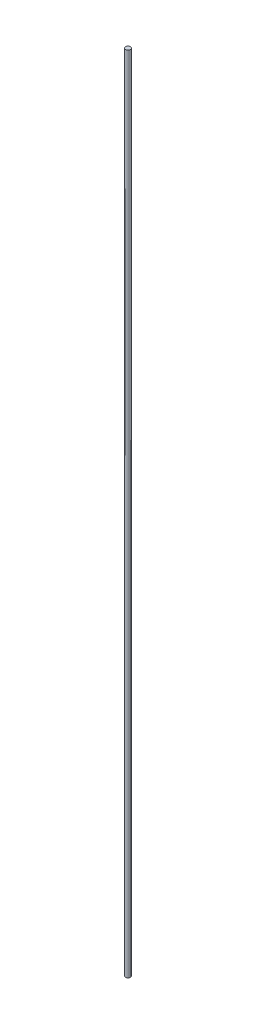
SolidWorks part; units mm, degrees
ref_plane "Спереди" through (0, 0, 0) normal (0, 0, 1) x (1, 0, 0)
ref_plane "Сверху" through (0, 0, 0) normal (0, 1, 0) x (1, 0, 0)
ref_plane "Справа" through (0, 0, 0) normal (1, 0, 0) x (0, 0, -1)
sketch "Эскиз2" plane through (0, 0, 0) normal (0, 0, 1) x (1, 0, 0)
  line L0 (0, 326.1485) -> (-5, 326.1485) construction
  line L5 (-2.5, 326.1485) -> (0, 326.1485)
  line L6 (-2.5, 326.1485) -> (-2.5, -480.4515)
  line L7 (-2.5, -480.4515) -> (0, -480.4515)
  line L8 (0, 326.1485) -> (0, -480.4515)
  line L9 (-2.5, 326.1485) -> (0, -480.4515) construction
  line L10 (-2.5, -480.4515) -> (0, 326.1485) construction
  line L13 (-506.5, -480.4515) -> (23.5, -480.4515) construction
  point P0 (-1.25, -77.1515)
  point P12 (0, 0)
  dimension "D1" = 2.5
revolve "Повернуть1" add sketch "Эскиз2" angle 360 about L6
equation "\"Ширина груза\"= 420"
equation "\"Глубина груза\"= 490"
equation "\"Высота груза\"= 297"
equation "\"Ширина ячейки\"= \"Ширина груза\" + 10"
equation "\"Глубина ячейки\"= \"Глубина груза\" + 10"
equation "\"Высота ячейки\"= \"Высота груза\" + 10 + 13"
equation "\"Колво ячеек ширина\"= 2"
equation "\"Колво ячеек высота\"= 2"
equation "\"Толщина стенки\" = 6"
equation "\"Крепление дверцы\"= 5 "
equation "\"Ширина рейки\"= \"Толщина шестерни\""
equation "\"Высота рейки\"= 20"
equation "\"Высота пола\"= \"Толщина стенки\" * 2"
equation "\"Колво полозьев\"= 5"
equation "\"Отступ рейки\"= 20"
equation "\"Глубина каретки\"= \"Глубина ячейки\" + 30 + \"Мотор Y высота корпуса\" + 20"
equation "\"Длинна рейки\"= ( \"Ширина ячейки\" + \"Толщина стенки\" + \"Крепление дверцы\" ) * \"Колво ячеек ширина\" + \"Ширина ячейки выгрузки\" * \"Колво выгрузки\" + \"Толщина стенки\""
equation "\"Отступ шпильки\"= 26"
equation "\"Диаметр шпильки\"= 5"
equation "\"Длинна шпильки\"= ( \"Высота ячейки\" + \"Толщина стенки\" + \"Высота пола\" ) * \"Колво ячеек высота\" + ( \"Толщина стенки\" + \"Отступ рейки\" ) * 2 "
equation "\"D1@Эскиз2\"= \"Диаметр шпильки\" / 2"
equation "\"Ширина пластины\"= 50  "
equation "\"Высота зона выгрузки\"= \"Высота ячейки\" * 2 + \"Толщина стенки\" * 2"
equation "\"Колво выгрузки\"= 1"
equation "\"Отступ крепления мотора фиксации\" = 30"
equation "\"Мотор X ширина корпуса\"= 42.3"
equation "\"Мотор X высота корпуса\"= 42.3"
equation "\"Мотор X длина корпуса\"= 40"
equation "\"Мотор X вылет вала\"= 19.8"
equation "\"Мотор Y ширина корпуса\"= 42.3"
equation "\"Мотор Y высота корпуса\"= 42.3"
equation "\"Мотор Y длина корпуса\"= 48"
equation "\"Мотор Y вылет вала\"= 30"
equation "\"Мотор Z ширина корпуса\"= 42"
equation "\"Мотор Z высота корпуса\"= 42"
equation "\"Мотор Z длина корпуса\"= 40"
equation "\"Мотор Z вылет вала\"= 23"
equation "\"Мотор диаметр вала ПРЕДВ\"= 5"
equation "\"Мотор шаг крепления ПРЕДВ\"= 31"
equation "\"Мотор диаметр отверстий ПРЕДВ\"= 3"
equation "\"Мотор глубина отверстий ПРЕДВ\"= 4.5"
equation "\"Мотор диаметр буртика ПРЕДВ\"= 22"
equation "\"Мотор высота буртика ПРЕДВ\"= 2"
equation "\"Мотор диаметр шкива ПРЕДВ\"= 16"
equation "\"Мотор длина шкива ПРЕДВ\"= 12"
equation "\"Мотор отступ шкива ПРЕДВ\"= 5"
equation "\"Мотор X шаг градусов\"= 1.8"
equation "\"Мотор X ток А\"= 1.5"
equation "\"Мотор X сопротивление Ом\"= 1.3"
equation "\"Мотор X индуктивность мГн\"= 2"
equation "\"Мотор Y шаг градусов\"= 1.8"
equation "\"Мотор Y ток А\"= 2.2"
equation "\"Мотор Y сопротивление Ом\"= 0.9"
equation "\"Мотор Y индуктивность мГн\"= 2"
equation "\"Мотор Z шаг градусов\"= 1.8"
equation "\"Мотор Z ток А\"= 1"
equation "\"Мотор Z сопротивление Ом\"= 4"
equation "\"Мотор Z индуктивность мГн\"= 8"
equation "\"Мотор Y диаметр ротора\"= 25.78"
equation "\"Ширина ячейки выгрузки\"= \"Ширина ячейки\" + \"Толщина стенки\" + \"Отступ крепления мотора фиксации\"*2"
